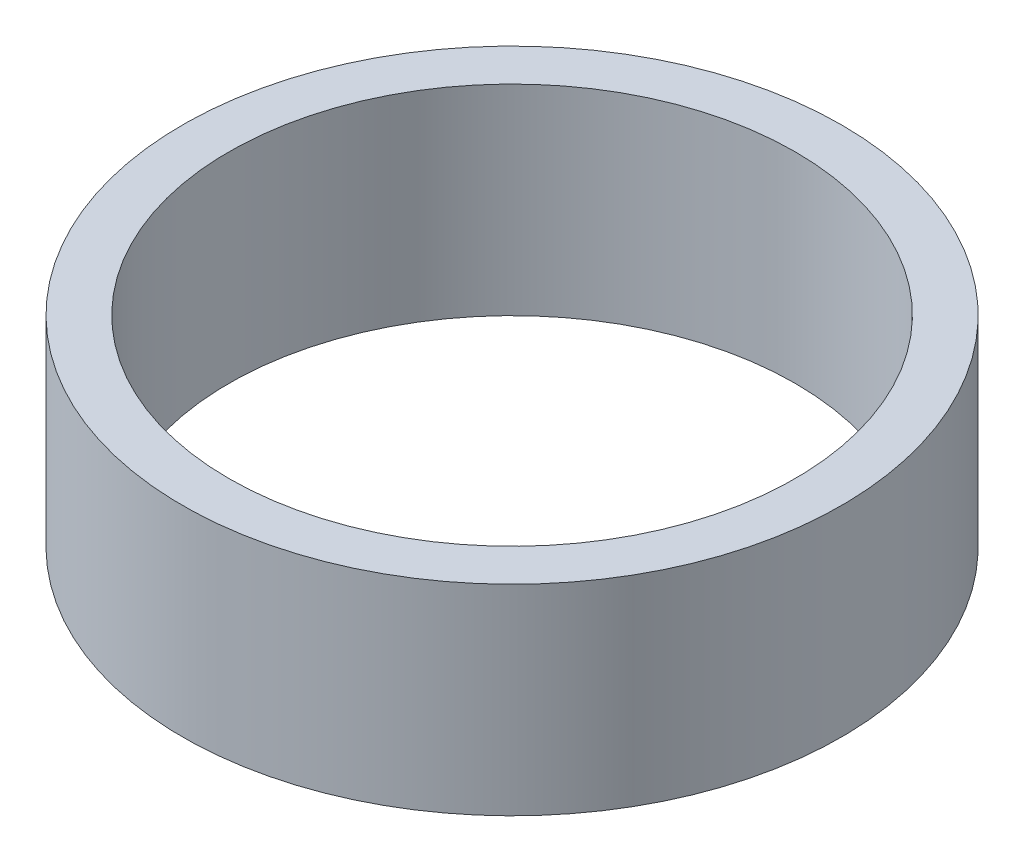
SolidWorks part; units mm, degrees
ref_plane "Front Plane" through (0, 0, 0) normal (0, 0, 1) x (1, 0, 0)
ref_plane "Top Plane" through (0, 0, 0) normal (0, 1, 0) x (1, 0, 0)
ref_plane "Right Plane" through (0, 0, 0) normal (1, 0, 0) x (0, 0, -1)
sketch "Sketch1" plane through (0, 0, 0) normal (0, 1, 0) x (1, 0, 0)
  circle A0 centre (0, 0) radius 22.5
  dimension "SLEEVE_OD" = 45
extrude "Boss-Extrude1" add sketch "Sketch1" along normal blind 13.6927
sketch "Sketch2" plane through (0, 0, 0) normal (0, 1, 0) x (1, 0, 0)
  circle A0 centre (0, 0) radius 19.326
  dimension "BORE_D" = 38.6519
extrude "Cut-Extrude1" cut sketch "Sketch2" along normal through all
chamfer "Chamfer1" distance 1.8987 angle 45 rebuild error yes
